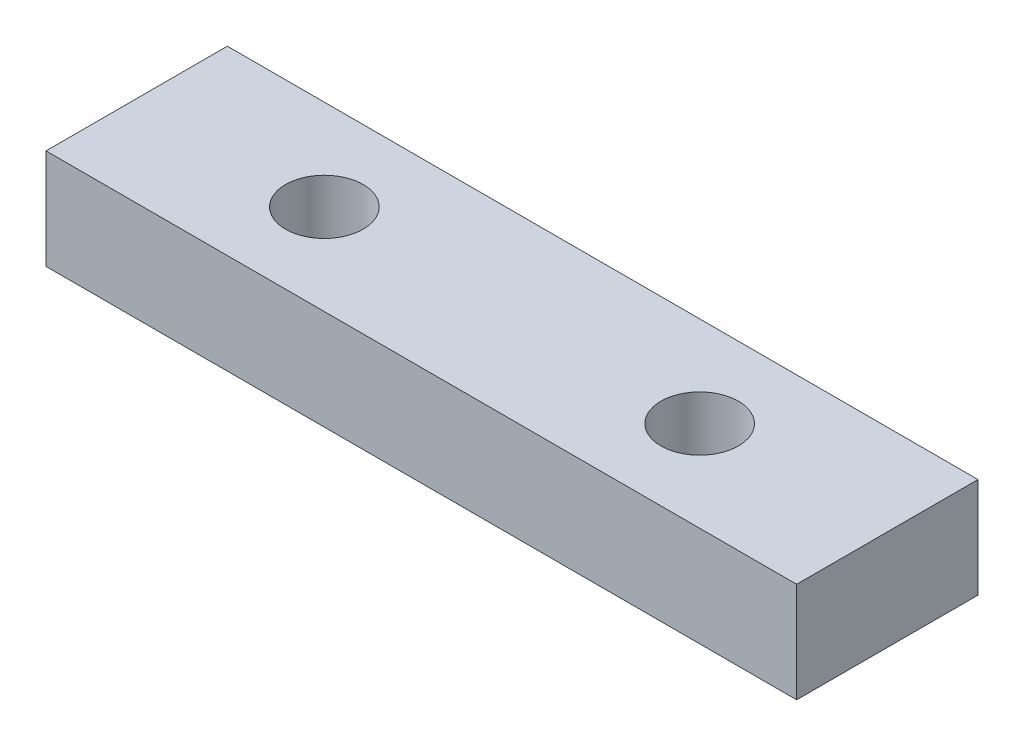
SolidWorks part; units mm, degrees
material "PLA Black"
ref_plane "Front" through (0, 0, 0) normal (0, 0, 1) x (1, 0, 0)
ref_plane "Top" through (0, 0, 0) normal (0, 1, 0) x (1, 0, 0)
ref_plane "Right" through (0, 0, 0) normal (1, 0, 0) x (0, 0, -1)
sketch "Sketch1" plane through (0, 0, 0) normal (0, 1, 0) x (1, 0, 0)
  line L0 (-13.9058, -3.6239) -> (9.3641, -3.6239) construction
  line L1 (0, 6.301) -> (0, -4.9245) construction
  line L2 (15, 0) -> (15, -7.2479) construction
  line L3 (-15, 0) -> (15, 0)
  line L4 (-15, 0) -> (-15, -7.2479)
  line L5 (-15, -7.2479) -> (15, -7.2479)
  line L6 (15, 0) -> (15, -7.2479)
  line L7 (-15, -7.2479) -> (-2.9554, -7.2479) construction
  circle A0 centre (7.5, -3.6239) radius 1.55
  circle A1 centre (-7.5, -3.6239) radius 1.55
  dimension "D3" = 3.1
  dimension "D4" = 15
extrude "Boss-Extrude1" add sketch "Sketch1" along normal blind 4 contours L3 L6 L5 L4 | A1 | A0
